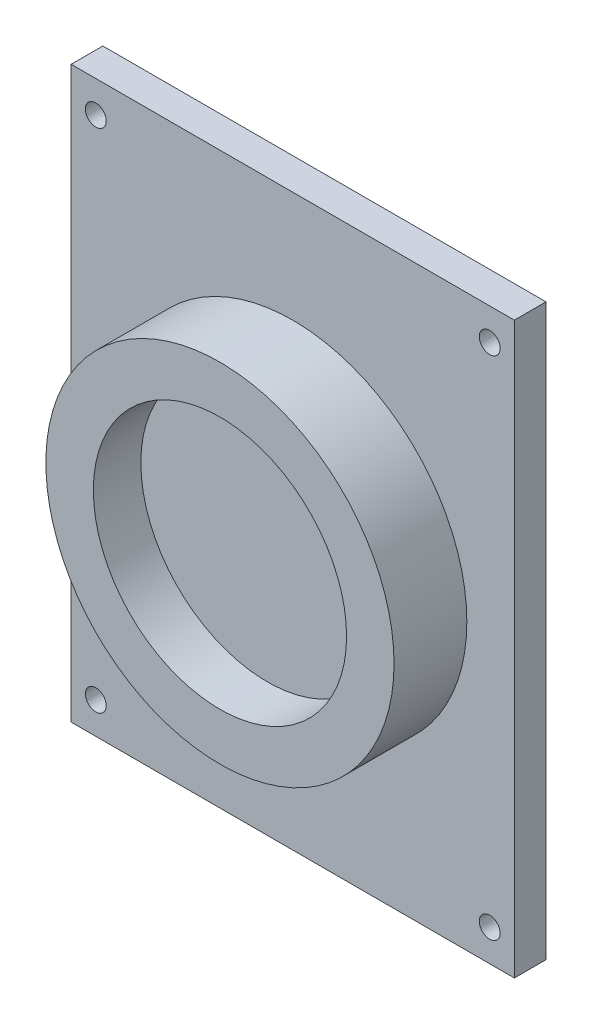
SolidWorks part; units mm, degrees
ref_plane "Alzado" through (0, 0, 0) normal (0, 0, 1) x (1, 0, 0)
ref_plane "Planta" through (0, 0, 0) normal (0, 1, 0) x (1, 0, 0)
ref_plane "Vista lateral" through (0, 0, 0) normal (1, 0, 0) x (0, 0, -1)
sketch "Croquis1" plane through (0, 0, 0) normal (0, 0, 1) x (1, 0, 0)
  line L0 (0, 0) -> (140, 0)
  line L1 (140, 0) -> (140, 180)
  line L2 (140, 180) -> (0, 180)
  line L3 (0, 180) -> (0, 0)
  line L4 (0, 180) -> (140, 0) construction
  line L5 (140, 180) -> (0, 0) construction
  dimension "D1" = 140
  dimension "D2" = 180
extrude "Saliente-Extruir1" add sketch "Croquis1" along normal blind 10
sketch "Croquis2" plane through (0, 0, 10) normal (0, 0, 1) x (1, 0, 0)
  line L0 (0, 180) -> (140, 0) construction
  line L1 (0, 0) -> (140, 0) construction
  line L2 (140, 180) -> (0, 0) construction
  circle A0 centre (70, 90) radius 55
extrude "Saliente-Extruir2" add sketch "Croquis2" along normal blind 8
sketch "Croquis3" plane through (0, 0, 18) normal (0, 0, 1) x (1, 0, 0)
  circle A0 centre (70, 90) radius 40
  circle A1 centre (70, 90) radius 55
extrude "Saliente-Extruir3" add sketch "Croquis3" along normal blind 15
ref_plane "Plano1" through (140, 180, 0) normal (0, 1, 0) x (1, 0, 0)
sketch "Croquis4" plane through (0, 0, 0) normal (0, 0, -1) x (-1, 0, 0)
  line L0 (0, 180) -> (-140, 0) construction
  line L1 (-140, 180) -> (0, 0) construction
  line L2 (-140, 180) -> (0, 180) construction
  line L3 (-132.2222, 10) -> (-7.7778, 10)
  line L4 (-132.2222, 10) -> (-132.2222, 170)
  line L5 (-132.2222, 170) -> (-7.7778, 170)
  line L6 (-7.7778, 10) -> (-7.7778, 170)
  line L7 (-132.2222, 10) -> (-7.7778, 170) construction
  line L8 (-132.2222, 170) -> (-7.7778, 10) construction
  point P8 (-70, 90)
  dimension "D1" = 10
hole_wizard "Refrentado para tornillo con cabeza plana de M61" positions "Croquis6" profile "Croquis7" counterbore size "M6" standard "DIN" end condition through all
sketch "Croquis6" plane through (0, 0, 0) normal (0, 0, -1) x (-1, 0, 0)
  point P0 (-132.2222, 170)
  point P3 (-7.7778, 170)
  point P6 (-7.7778, 10)
  point P9 (-132.2222, 10)
sketch "Croquis7" plane through (132.2222, 170, 0) normal (1, 0, 0) x (0, 1, 0)
  line L0 (0, 0) -> (0, 33)
  line L1 (0, 33) -> (3.3, 33)
  line L3 (3.3, 33) -> (3.3, 3.9)
  line L4 (3.3, 3.9) -> (5.5, 3.9)
  line L5 (5.5, 3.9) -> (5.5, 0)
  line L7 (5.5, 0) -> (0, 0)
  line L11 (0, -6.35) -> (0, 107.95) construction
  dimension "Diámetro de taladro hasta el siguiente" = 6.6
  dimension "Profundidad de taladro hasta el siguiente" = 33
  dimension "Diámetro de refrentado" = 11
  dimension "Profundidad de refrentado" = 3.9
